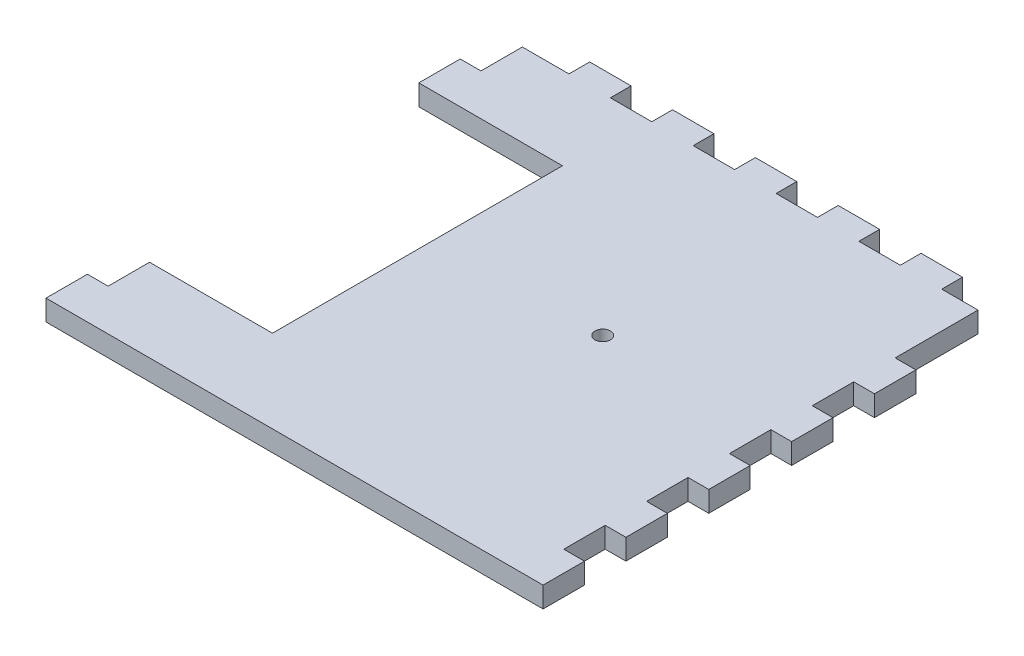
SolidWorks part; units mm, degrees
ref_plane "Front Plane" through (0, 0, 0) normal (0, 0, 1) x (1, 0, 0)
ref_plane "Top Plane" through (0, 0, 0) normal (0, 1, 0) x (1, 0, 0)
ref_plane "Right Plane" through (0, 0, 0) normal (1, 0, 0) x (0, 0, -1)
sketch "Sketch1" plane through (0, 0, 0) normal (0, 1, 0) x (1, 0, 0)
  line L1 (-139.7, -139.7) -> (139.7, -139.7)
  line L2 (-139.7, -139.7) -> (-139.7, 139.7)
  line L3 (-139.7, 139.7) -> (139.7, 139.7)
  line L4 (139.7, -139.7) -> (139.7, 139.7)
  line L5 (-139.7, -139.7) -> (139.7, 139.7) construction
  line L6 (-139.7, 139.7) -> (139.7, -139.7) construction
  point P0 (0, 0)
  dimension "D1" = 279.4
  dimension "D2" = 279.4
extrude "Boss-Extrude1" add sketch "Sketch1" along normal blind 12.7
sketch "Sketch2" plane through (139.7, 0, 0) normal (1, 0, 0) x (0, 0, -1)
  line L0 (-139.7, 12.7) -> (139.7, 12.7) construction
  line L1 (-139.7, 0) -> (-114.3, 0)
  line L2 (-139.7, 0) -> (-139.7, 12.7)
  line L3 (-139.7, 12.7) -> (-114.3, 12.7)
  line L4 (-114.3, 0) -> (-114.3, 12.7)
  dimension "D1" = 25.4
extrude "Boss-Extrude2" add sketch "Sketch2" along normal blind 12.7
pattern_linear "LPattern1" count 5 spacing 50.8 along (0, 0, -1) of "Boss-Extrude2"
mirror "Mirror1" about plane through (0, 0, 0) normal (1, 0, 0) of "LPattern1"
sketch "Sketch3" plane through (0, 0, -139.7) normal (0, 0, -1) x (-1, 0, 0)
  line L0 (-139.7, 12.7) -> (139.7, 12.7) construction
  line L1 (-117.475, 12.7) -> (-92.075, 12.7)
  line L2 (-117.475, 12.7) -> (-117.475, 0)
  line L3 (-117.475, 0) -> (-92.075, 0)
  line L4 (-92.075, 12.7) -> (-92.075, 0)
  line L5 (-139.7, 0) -> (139.7, 0) construction
  line L7 (-152.4, 0) -> (-152.4, 12.7) construction
  dimension "D1" = 34.925
  dimension "D2" = 25.4
extrude "Boss-Extrude3" add sketch "Sketch3" along normal blind 12.7
pattern_linear "LPattern2" count 5 spacing 50.8 along (-1, 0, 0) of "Boss-Extrude3"
sketch "Sketch6" plane through (0, 12.7, 0) normal (0, 1, 0) x (1, 0, 0)
  line L0 (41.275, 139.7) -> (15.875, 139.7) construction
  line L1 (139.7, -12.7) -> (139.7, 12.7) construction
  circle A0 centre (38.1, 11.176) radius 4.7625
  dimension "D1" = 128.524
  dimension "D3" = 9.525
  dimension "D2" = 101.6
extrude "Cut-Extrude1" cut sketch "Sketch6" against normal through all
sketch "Sketch8" plane through (0, 12.7, 0) normal (0, 1, 0) x (1, 0, 0)
  line L1 (-152.4, 88.9) -> (-64.3339, 88.9)
  line L2 (-152.4, 88.9) -> (-152.4, -88.9)
  line L3 (-152.4, -88.9) -> (-64.3339, -88.9)
  line L4 (-64.3339, 88.9) -> (-64.3339, -88.9)
  dimension "D1" = 177.8
extrude "Cut-Extrude3" cut sketch "Sketch8" against normal through all
sketch "Sketch7" plane through (0, 12.7, 0) normal (0, 1, 0) x (1, 0, 0)
  line L2 (-111.125, 139.7) -> (-139.7, 139.7) construction
  line L3 (-139.7, 139.7) -> (-139.7, 88.9) construction
  circle A0 centre (-101.6, 65.278) radius 5.08
  circle A1 centre (-101.6, 27.686) radius 5.08
  dimension "D1" = 10.16
  dimension "D2" = 10.16
  dimension "D3" = 38.1
  dimension "D5" = 37.592
  dimension "D6" = 74.422
sketch "Sketch9" plane through (-139.7, 0, 0) normal (-1, 0, 0) x (0, 0, 1)
  line L0 (153.67, 0) -> (-153.67, 0) construction
  line L1 (-88.9, 12.7) -> (-114.3, 12.7)
  line L2 (-88.9, 12.7) -> (-88.9, 0)
  line L3 (-88.9, 0) -> (-114.3, 0)
  line L4 (-114.3, 12.7) -> (-114.3, 0)
  dimension "D1" = 25.4
extrude "Boss-Extrude4" add sketch "Sketch9" along normal blind 12.7
